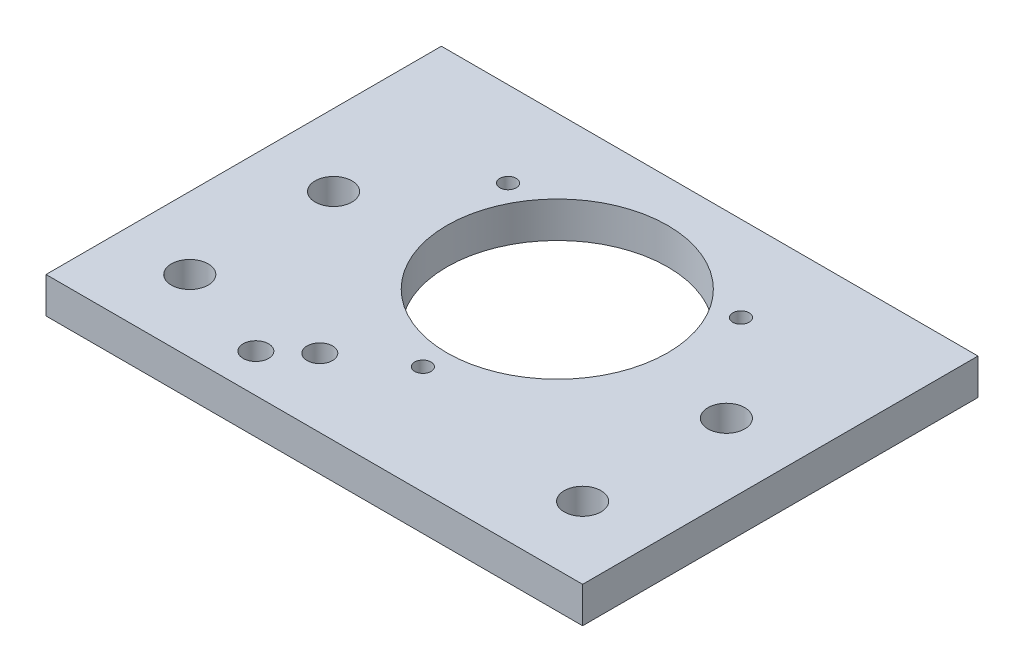
SolidWorks part; units mm, degrees
ref_plane "Front Plane" through (0, 0, 0) normal (0, 0, 1) x (1, 0, 0)
ref_plane "Top Plane" through (0, 0, 0) normal (0, 1, 0) x (1, 0, 0)
ref_plane "Right Plane" through (0, 0, 0) normal (1, 0, 0) x (0, 0, -1)
sketch "Sketch1" plane through (0, 0, 0) normal (0, 1, 0) x (1, 0, 0)
  line L0 (-34.7, 3.175) -> (34.7, 3.175) construction
  line L1 (-47.4, 34.925) -> (47.4, 34.925)
  line L2 (-47.4, 34.925) -> (-47.4, -34.925)
  line L3 (-47.4, -34.925) -> (47.4, -34.925)
  line L4 (47.4, 34.925) -> (47.4, -34.925)
  line L5 (-47.4, 34.925) -> (47.4, -34.925) construction
  line L6 (-47.4, -34.925) -> (47.4, 34.925) construction
  line L7 (22, -34.925) -> (47.4, -34.925) construction
  line L8 (-17.1383, -28.1118) -> (-11.1649, -22.7903) construction
  line L9 (-34.7, -22.225) -> (34.7, -22.225) construction
  line L10 (-34.7, -22.225) -> (-34.7, 22.225) construction
  line L11 (-34.7, 22.225) -> (34.7, 22.225) construction
  line L12 (34.7, -22.225) -> (34.7, 22.225) construction
  line L13 (-34.7, -22.225) -> (34.7, 22.225) construction
  line L14 (-34.7, 22.225) -> (34.7, -22.225) construction
  line L15 (0, 0) -> (0, 8) construction
  line L16 (-19.7991, -25.1251) -> (-13.8257, -19.8036) construction
  line L17 (22, -34.925) -> (22, -9.525) construction
  line L18 (22, -9.525) -> (47.4, -9.525) construction
  line L19 (47.4, -34.925) -> (47.4, -9.525) construction
  line L20 (22, -34.925) -> (47.4, -9.525) construction
  line L21 (22, -9.525) -> (47.4, -34.925) construction
  line L22 (0, 8) -> (0, -15.75) construction
  line L23 (0, 8) -> (20.5681, 19.875) construction
  line L24 (0, 8) -> (-20.5681, 19.875) construction
  line L25 (-14.4776, -31.0985) -> (-8.5042, -25.7771) construction
  line L27 (-47.4, -34.925) -> (-22, -34.925)
  line L28 (-47.4, -34.925) -> (-47.4, -9.525)
  line L29 (-47.4, -9.525) -> (-22, -9.525) construction
  line L30 (-22, -34.925) -> (-22, -9.525) construction
  circle A18 centre (-34.7, 22.225) radius 3.2576 construction
  circle A19 centre (34.7, 22.225) radius 3.2576 construction
  circle A20 centre (34.7, -22.225) radius 3.2576
  circle A21 centre (-34.7, -22.225) radius 3.2576
  circle A22 centre (-11.1649, -22.7903) radius 2.25
  circle A24 centre (0, 8) radius 19.5
  circle A25 centre (0, 8) radius 23.75 construction
  circle A30 centre (-34.7, 3.175) radius 3.2576
  circle A31 centre (34.7, 3.175) radius 3.2576
  circle A32 centre (0, -15.75) radius 1.45
  circle A33 centre (-20.5681, 19.875) radius 1.45
  circle A34 centre (20.5681, 19.875) radius 1.45
  circle A35 centre (0, 8) radius 26.5 construction
  circle A36 centre (-17.1383, -28.1118) radius 2.25
  arc A37 (-19.7991, -25.1251) -> (-14.4776, -31.0985) centre (-17.1383, -28.1118) ccw construction
  arc A38 (-8.5042, -25.7771) -> (-13.8257, -19.8036) centre (-11.1649, -22.7903) ccw construction
  circle A39 centre (-11.1649, -22.7903) radius 6 construction
  point P11 (-14.1516, -25.4511)
  point P51 (0, 34.5)
  point P55 (-11.1649, -22.7903)
  dimension "D2" = 8
  dimension "D4" = 39
  dimension "D7" = 47.5
  dimension "D10" = 120
  dimension "D13" = 12.7
  dimension "D15" = 6.5151
  dimension "D16" = 4
  dimension "D17" = 4.5
  dimension "D9" = 120
  dimension "D5" = 8
  dimension "D12" = 2.9
  dimension "D18" = 53
  dimension "D19" = 12
  dimension "D6" = 94.8
  dimension "D8" = 69.85
  dimension "D11" = 25.4
  dimension "D14" = 12.7
  dimension "D3" = 25.4
extrude "Boss-Extrude1" add sketch "Sketch1" along normal blind 6.35 contours L4 L1 L2 L3 A36 A34 A33 A32 A31 A30 A24 A22 A21 A20 region at (0, 0, -33.7475)
sketch "Sketch4" plane through (0, 0, 0) normal (0, -1, 0) x (1, 0, 0)
  line L6 (-17.1383, 28.1118) -> (-11.1649, 22.7903) construction
  line L7 (-14.145, 31.4719) -> (-8.1716, 26.1504)
  line L8 (-20.1317, 24.7518) -> (-14.1582, 19.4303)
  circle A6 centre (-11.1649, 22.7903) radius 2.25 construction
  circle A7 centre (-17.1383, 28.1118) radius 2.25 construction
  circle A8 centre (-11.1649, 22.7903) radius 2.25
  circle A9 centre (-17.1383, 28.1118) radius 2.25
  arc A10 (-14.145, 31.4719) -> (-20.1317, 24.7518) centre (-17.1383, 28.1118) ccw
  arc A11 (-14.1582, 19.4303) -> (-8.1716, 26.1504) centre (-11.1649, 22.7903) ccw
  point P23 (-14.1516, 25.4511)
  dimension "D2" = 4.5
extrude "Cut-Extrude2" cut sketch "Sketch4" against normal blind 3 contours L8 A11 L7 A10 A9 A8 region at (-14.1516, 0, 25.4511)
equation "\"testbed_height\" = 91.50mm"
equation "\"plate_thickness\" = 6mm"
equation "\"main_body_splay_length\" = 48.5mm"
equation "\"splay_shaft_length_no_wires\" = 10mm"
equation "\"splay_shaft_length_wires\" = 6.5mm"
equation "\"timing_pulley_offset\" = 0mm"
equation "\"effective_motor_length\" = \"timing_pulley_offset\" + \"splay_shaft_length_no_wires\" + \"main_body_splay_length\""
equation "\"80_20_side\" = 25.4mm"
equation "\"80_20_length\" = 152.4mm"
equation "\"80_20_optic_mount_length\" = \"80_20_length\" - 25.4mm"
equation "\"optic_board_hole_size\" = 6.35mm"
equation "\"total_mounting_length\" = \"testbed_height\" - \"effective_motor_length\" - \"80_20_side\""
equation "\"mounting_vertical_portion_height\" = \"total_mounting_length\" - 2 * \"plate_thickness\""
equation "\"face_mount_width\" = 15.25mm"
equation "\"center_dist_to_face_mount_vertical_screws\" = 5mm"
equation "\"D1@Boss-Extrude1\"=0.25in"
